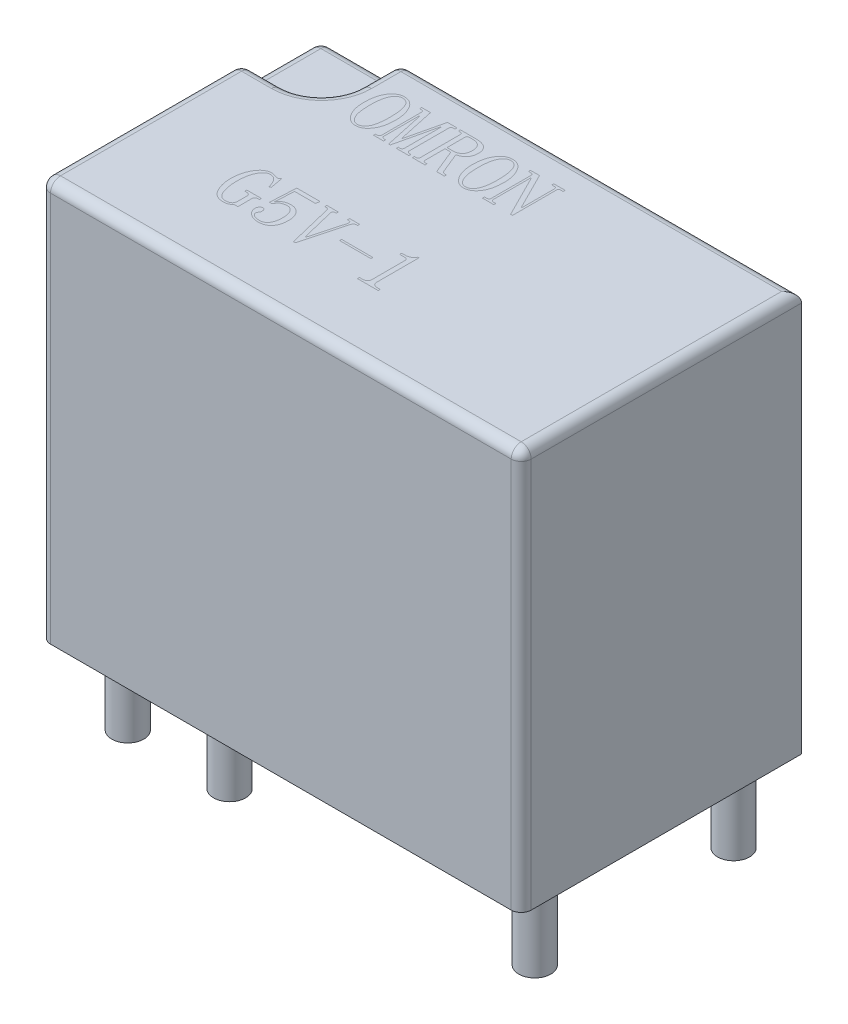
SolidWorks part; units mm, degrees
ref_plane "前视基准面" through (0, 0, 0) normal (0, 0, 1) x (1, 0, 0)
ref_plane "上视基准面" through (0, 0, 0) normal (0, 1, 0) x (1, 0, 0)
ref_plane "右视基准面" through (0, 0, 0) normal (1, 0, 0) x (0, 0, -1)
sketch "草图1" plane through (0, 0, 0) normal (0, 1, 0) x (1, 0, 0)
  line L0 (0, 0) -> (0, 7)
  line L1 (0, 7) -> (12, 7)
  line L2 (12, 7) -> (12, 0)
  line L3 (12, 0) -> (0, 0)
  dimension "D1" = 7
  dimension "D2" = 12
extrude "凸台-拉伸1" add sketch "草图1" along normal blind 10
sketch "草图2" plane through (0, 10, 0) normal (0, 1, 0) x (1, 0, 0)
  line L0 (1.9965, 6.0195) -> (1.9965, 7)
  line L1 (12, 7) -> (0, 7) construction
  line L2 (0.9965, 5.0195) -> (0, 5.0195)
  line L3 (0, 7) -> (0, 0) construction
  line L4 (1.9965, 7) -> (0, 7)
  line L5 (0, 7) -> (0, 5.0195)
  arc A1 (0.9965, 5.0195) -> (1.9965, 6.0195) centre (0.9965, 6.0195) ccw
extrude "切除-拉伸1" cut sketch "草图2" against normal blind 0.5
fillet "圆角1" radius 0.25 15 edges at (12, 10, -3.5) (12, 5, 0) (6, 10, 0) (0, 5, 0) (0.4983, 9.5, -5.0195) (1.9965, 9.5, -6.5098) (1.7036, 9.5, -5.3124) (0, 10, -2.5098) (0, 9.5, -6.0098) (0.4983, 10, -5.0195) (1.7036, 10, -5.3124) (1.9965, 10, -6.5098) (6.9983, 10, -7) (0.9983, 9.5, -7) (0, 4.75, -7)
sketch "草图3" plane through (0, 0, 0) normal (0, -1, 0) x (1, 0, 0)
  line L0 (0, -6.75) -> (0, -0.25) construction
  line L1 (0.25, 0) -> (11.75, 0) construction
  line L2 (0, -3.5) -> (12, -3.625) construction
  line L3 (12, -0.25) -> (12, -7) construction
  circle A0 centre (1.07, -1.11) radius 0.4
  circle A1 centre (3.61, -1.11) radius 0.4
  circle A2 centre (11.1778, -6.1234) radius 0.4
  circle A3 centre (3.5594, -5.9647) radius 0.4
  circle A4 centre (11.23, -1.11) radius 0.4
  circle A5 centre (6.15, -1.11) radius 0.4 [skipped]
  circle A6 centre (8.69, -1.11) radius 0.4 [skipped]
  circle A7 centre (1.02, -5.9118) radius 0.4
  dimension "D1" = 0.8
  dimension "D2" = 1.07
  dimension "D3" = 1.11
  dimension "D5" = 2.54
  dimension "D4" = 5
extrude "凸台-拉伸2" add sketch "草图3" along normal blind 2
sketch "草图4" plane through (0, 10, 0) normal (0, 1, 0) x (-1, 0, 0)
  line L0 (-2.3814, -5) -> (-11.3048, -5) construction
  line L1 (-2.2465, -7) -> (-12, -7) construction
  text T0 "OMRON \r\nG5V-1" height 1.2
  dimension "D1" = 2
wrap "包覆1" sketch "草图4" wrap type scribe source sketch "草图4" face at (4.2498, 10, -4.1857)
